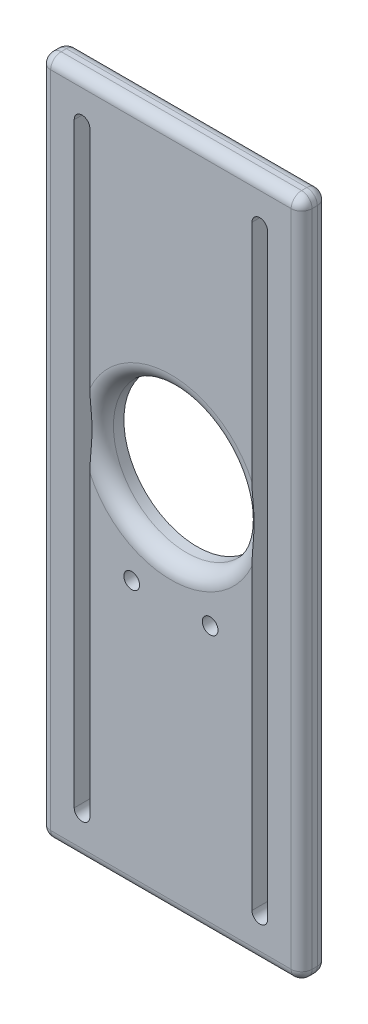
SolidWorks part; units mm, degrees
ref_plane "Front Plane" through (0, 0, 0) normal (0, 0, 1) x (1, 0, 0)
ref_plane "Top Plane" through (0, 0, 0) normal (0, 1, 0) x (1, 0, 0)
ref_plane "Right Plane" through (0, 0, 0) normal (1, 0, 0) x (0, 0, -1)
sketch "Base" plane through (0, 0, 0) normal (0, 0, 1) x (1, 0, 0)
  line L0 (43.6224, 52.8458) -> (43.6224, 40.7373) construction
  line L1 (3.1224, 117.8458) -> (53.1224, 117.8458)
  line L2 (3.1224, 117.8458) -> (3.1224, -12.1542)
  line L3 (3.1224, -12.1542) -> (53.1224, -12.1542)
  line L4 (53.1224, 117.8458) -> (53.1224, -12.1542)
  line L8 (45.1224, 109.8458) -> (45.1224, -4.1542) construction
  line L9 (3.1224, 40.7373) -> (3.1224, 52.8458) construction
  line L12 (46.6224, 109.8458) -> (46.6224, -4.1542)
  line L13 (43.6224, 109.8458) -> (43.6224, -4.1542)
  line L14 (11.1224, 109.8458) -> (11.1224, -4.1542) construction
  line L15 (12.6224, 109.8458) -> (12.6224, -4.1542)
  line L16 (9.6224, 109.8458) -> (9.6224, -4.1542)
  circle A4 centre (28.1224, 59.8458) radius 14
  arc A5 (46.6224, 109.8458) -> (43.6224, 109.8458) centre (45.1224, 109.8458) ccw
  arc A6 (43.6224, -4.1542) -> (46.6224, -4.1542) centre (45.1224, -4.1542) ccw
  arc A7 (12.6224, 109.8458) -> (9.6224, 109.8458) centre (11.1224, 109.8458) ccw
  arc A8 (9.6224, -4.1542) -> (12.6224, -4.1542) centre (11.1224, -4.1542) ccw
  point P6 (28.1224, 117.8458)
  point P13 (45.1224, 52.8458)
  point P31 (11.1224, 52.8458)
  dimension "D5" = 28
  dimension "D6" = 17
  dimension "D4" = 8
  dimension "D11" = 114
  dimension "D2" = 8
  dimension "D7" = 130
  dimension "D8" = 50
  dimension "D9" = 17
  dimension "D10" = 50
  dimension "D12" = 3
extrude "Boss-Extrude1" add sketch "Base" along normal blind 5
sketch "Sketch4" plane through (0, 0, 5) normal (0, 0, 1) x (1, 0, 0)
  line L0 (28.1224, 45.8458) -> (53.1224, 45.8458) construction
  line L1 (53.1224, -12.1542) -> (53.1224, 117.8458) construction
  line L2 (53.1224, 45.8458) -> (53.1224, 32.1458) construction
  line L3 (53.1224, 32.1458) -> (3.1224, 32.1458) construction
  line L4 (3.1224, 117.8458) -> (3.1224, -12.1542) construction
  line L5 (3.1224, 32.1458) -> (3.1224, 45.8458) construction
  line L6 (3.1224, 45.8458) -> (28.1224, 45.8458) construction
  line L7 (3.1224, 38.9958) -> (20.6224, 38.9958) construction
  line L8 (53.1224, 38.9958) -> (35.6224, 38.9958) construction
  circle A0 centre (28.1224, 59.8458) radius 14 construction
  circle A1 centre (20.6224, 38.9958) radius 1.5
  circle A2 centre (35.6224, 38.9958) radius 1.5
  dimension "D1" = 17.5
  dimension "D4" = 3
  dimension "D2" = 15
  dimension "D3" = 13.7
fillet "Fillet3" radius 2 12 edges at (28.1224, -12.1542, 5) (28.1224, -12.1542, 0) (28.1224, 117.8458, 5) (28.1224, 117.8458, 0) (3.1224, 117.8458, 2.5) (3.1224, 52.8458, 5) (3.1224, -12.1542, 2.5) (3.1224, 52.8458, 0) (53.1224, -12.1542, 2.5) (53.1224, 52.8458, 5) (53.1224, 117.8458, 2.5) (53.1224, 52.8458, 0)
fillet "Fillet5" radius 3 1 edges at (42.1224, 59.8458, 5)
extrude "Cut-Extrude1" cut sketch "Sketch4" against normal blind 5
sketch "Sketch5" plane through (0, 0, 0) normal (0, 0, -1) x (-1, 0, 0)
  circle A0 centre (-20.6224, 38.9958) radius 3
  circle A1 centre (-35.6224, 38.9958) radius 3
  dimension "D1" = 6
extrude "Cut-Extrude2" cut sketch "Sketch5" against normal blind 2
